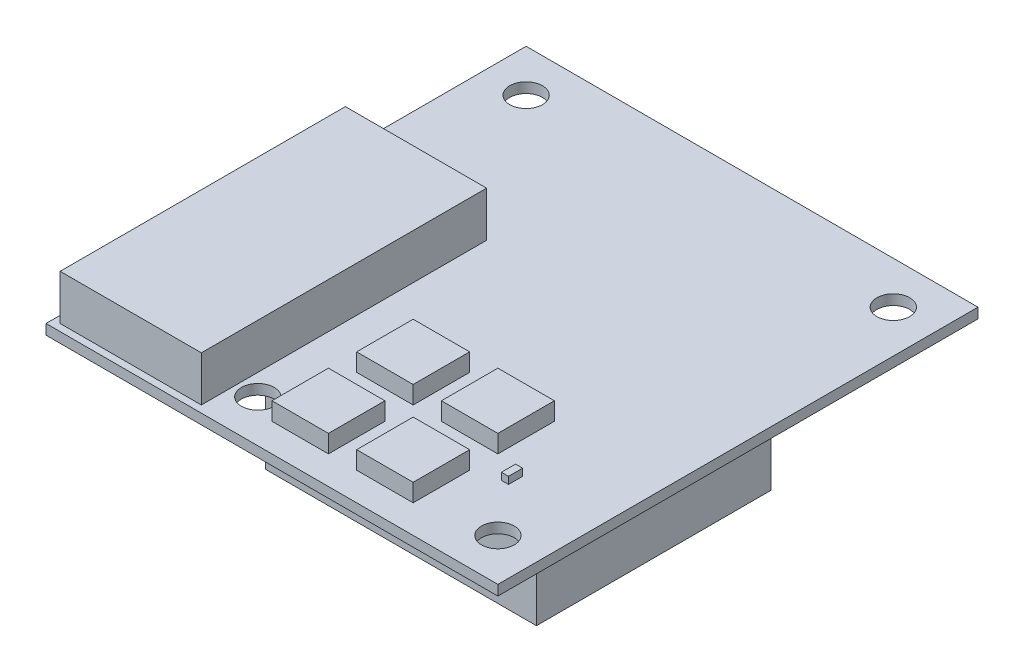
SolidWorks part; units mm, degrees
ref_plane "Front Plane" through (0, 0, 0) normal (0, 0, 1) x (1, 0, 0)
ref_plane "Top Plane" through (0, 0, 0) normal (0, 1, 0) x (1, 0, 0)
ref_plane "Right Plane" through (0, 0, 0) normal (1, 0, 0) x (0, 0, -1)
sketch "Sketch1" plane through (0, 0, 0) normal (0, 1, 0) x (1, 0, 0)
  line L1 (0, 0) -> (40.64, 0)
  line L2 (0, 0) -> (0, 43.18)
  line L3 (0, 43.18) -> (40.64, 43.18)
  line L4 (40.64, 0) -> (40.64, 43.18)
  dimension "D1" = 40.64
  dimension "D2" = 43.18
extrude "Boss-Extrude1" add sketch "Sketch1" along normal blind 0.9144
sketch "Sketch3" plane through (0, 0.9144, 0) normal (0, 1, 0) x (1, 0, 0)
  line L0 (0, 43.18) -> (0, 0) construction
  line L1 (17.78, 10.16) -> (22.86, 10.16)
  line L2 (17.78, 10.16) -> (17.78, 15.24)
  line L3 (17.78, 15.24) -> (22.86, 15.24)
  line L4 (22.86, 10.16) -> (22.86, 15.24)
  line L5 (17.78, 10.16) -> (22.86, 15.24) construction
  line L6 (17.78, 15.24) -> (22.86, 10.16) construction
  line L7 (0, 0) -> (40.64, 0) construction
  line L8 (30.48, 10.16) -> (30.48, 15.24)
  line L9 (25.4, 15.24) -> (30.48, 10.16) construction
  line L10 (25.4, 15.24) -> (30.48, 15.24)
  line L11 (25.4, 10.16) -> (25.4, 15.24)
  line L12 (25.4, 10.16) -> (30.48, 15.24) construction
  line L13 (25.4, 10.16) -> (30.48, 10.16)
  line L14 (30.48, 2.54) -> (30.48, 7.62)
  line L15 (25.4, 7.62) -> (30.48, 2.54) construction
  line L16 (25.4, 7.62) -> (30.48, 7.62)
  line L17 (25.4, 2.54) -> (25.4, 7.62)
  line L18 (25.4, 2.54) -> (30.48, 7.62) construction
  line L19 (25.4, 2.54) -> (30.48, 2.54)
  line L20 (22.86, 2.54) -> (22.86, 7.62)
  line L21 (17.78, 7.62) -> (22.86, 2.54) construction
  line L22 (17.78, 7.62) -> (22.86, 7.62)
  line L23 (17.78, 2.54) -> (17.78, 7.62)
  line L24 (17.78, 2.54) -> (22.86, 7.62) construction
  line L25 (17.78, 2.54) -> (22.86, 2.54)
  point P0 (20.32, 12.7)
  dimension "D1" = 20.32
  dimension "D2" = 12.7
  dimension "D3" = 5.08
  dimension "D4" = 2
  dimension "D5" = 2
extrude "Boss-Extrude2" add sketch "Sketch3" along normal blind 1.6
sketch "Sketch4" plane through (0, 0.9144, 0) normal (0, 1, 0) x (1, 0, 0)
  line L0 (0, 0) -> (40.64, 0) construction
  line L1 (0.635, 0.635) -> (13.335, 0.635)
  line L2 (0.635, 0.635) -> (0.635, 26.289)
  line L3 (0.635, 26.289) -> (13.335, 26.289)
  line L4 (13.335, 0.635) -> (13.335, 26.289)
  line L5 (0, 43.18) -> (0, 0) construction
  dimension "D1" = 0.635
  dimension "D2" = 0.635
  dimension "D3" = 25.654
  dimension "D4" = 12.7
extrude "Boss-Extrude3" add sketch "Sketch4" along normal blind 4.064
hole_wizard "#32 (0.116) Diameter Hole1" positions "Sketch7" profile "Sketch6" hole size "#32" standard "ANSI Inch"
sketch "Sketch7" plane through (0, 0.9144, 0) normal (0, 1, 0) x (1, 0, 0)
  line L0 (0, 0) -> (40.64, 0) construction
  line L1 (0, 43.18) -> (0, 0) construction
  point P0 (3.81, 39.37)
  point P2 (36.83, 39.37)
  point P4 (36.83, 3.81)
  point P6 (15.24, 3.81)
  dimension "D1" = 3.81
  dimension "D2" = 15.24
  dimension "D3" = 36.83
  dimension "D4" = 3.81
  dimension "D5" = 39.37
sketch "Sketch6" plane through (3.81, 0.9144, -39.37) normal (1, 0, 0) x (0, 0, 1)
  line L0 (0, 0) -> (0, 26.2852)
  line L1 (0, 26.2852) -> (1.4732, 25.4)
  line L2 (1.4732, 25.4) -> (1.4732, 0)
  line L5 (1.4732, 0) -> (0, 0)
  line L10 (0, 26.2852) -> (-1.4732, 25.4) construction
  line L11 (0, -6.35) -> (0, 107.95) construction
  dimension "Hole Dia." = 2.9464
  dimension "Hole Depth" = 25.4
  dimension "Drill Angle" = 118
sketch "Sketch8" plane through (0, 0.9144, 0) normal (0, 1, 0) x (1, 0, 0)
  line L0 (0, 0) -> (40.64, 0) construction
  line L1 (32.7025, 8.255) -> (33.3375, 8.255)
  line L2 (32.7025, 8.255) -> (32.7025, 9.525)
  line L3 (32.7025, 9.525) -> (33.3375, 9.525)
  line L4 (33.3375, 8.255) -> (33.3375, 9.525)
  line L5 (32.7025, 8.255) -> (33.3375, 9.525) construction
  line L6 (32.7025, 9.525) -> (33.3375, 8.255) construction
  line L8 (0, 43.18) -> (0, 0) construction
  point P0 (33.02, 8.89)
  point P9 (0, 7.3188)
  dimension "D1" = 8.89
  dimension "D2" = 33.02
  dimension "D3" = 0.635
  dimension "D4" = 1.27
extrude "Boss-Extrude4" add sketch "Sketch8" along normal blind 0.635
sketch "Sketch10" plane through (0, 0, 0) normal (0, -1, 0) x (1, 0, 0)
  line L0 (-0.6651, -32.8564) -> (10.4452, -42.179)
  line L1 (-0.6651, -32.8564) -> (5.1146, -25.9684)
  line L2 (10.4452, -42.179) -> (16.2248, -35.291)
  line L3 (5.1146, -25.9684) -> (16.2248, -35.291)
  line L4 (-0.6651, -32.8564) -> (16.2248, -35.291) construction
  line L5 (10.4452, -42.179) -> (5.1146, -25.9684) construction
  line L7 (0, -43.18) -> (0, 0) construction
  line L9 (0, 0) -> (40.64, 0) construction
  line L10 (40.64, -43.18) -> (0, -43.18) construction
  point P0 (13.335, -38.735)
  point P1 (7.7799, -34.0737)
  point P10 (9.7016, 0)
  dimension "D1" = 13.335
  dimension "D2" = 38.735
  dimension "D3" = 8.9916
  dimension "D4" = 14.5034
  dimension "D5" = 40
extrude "Boss-Extrude5" add sketch "Sketch10" along normal blind 10.9982
sketch "Sketch11" plane through (0, 0, 0) normal (0, -1, 0) x (1, 0, 0)
  line L0 (37.592, -27.5971) -> (29.9974, -34.1249)
  line L1 (37.592, -6.5151) -> (13.208, -6.5151)
  line L2 (37.592, -6.5151) -> (37.592, -27.5971)
  line L3 (37.592, -27.5971) -> (13.208, -27.5971) construction
  line L4 (13.208, -6.5151) -> (13.208, -27.5971)
  line L5 (29.9974, -34.1249) -> (20.8026, -34.1249)
  line L6 (20.8026, -34.1249) -> (13.208, -27.5971)
  line L7 (25.4, -34.1249) -> (25.4, -6.5151) construction
  line L8 (0, -32.0637) -> (0, 0) construction
  line L9 (0, 0) -> (40.64, 0) construction
  point P8 (25.4, -20.32)
  dimension "D1" = 24.384
  dimension "D2" = 6.5278
  dimension "D3" = 27.6098
  dimension "D4" = 7.5946
  dimension "D5" = 25.4
  dimension "D6" = 20.32
extrude "Boss-Extrude6" add sketch "Sketch11" along normal blind 7.09
